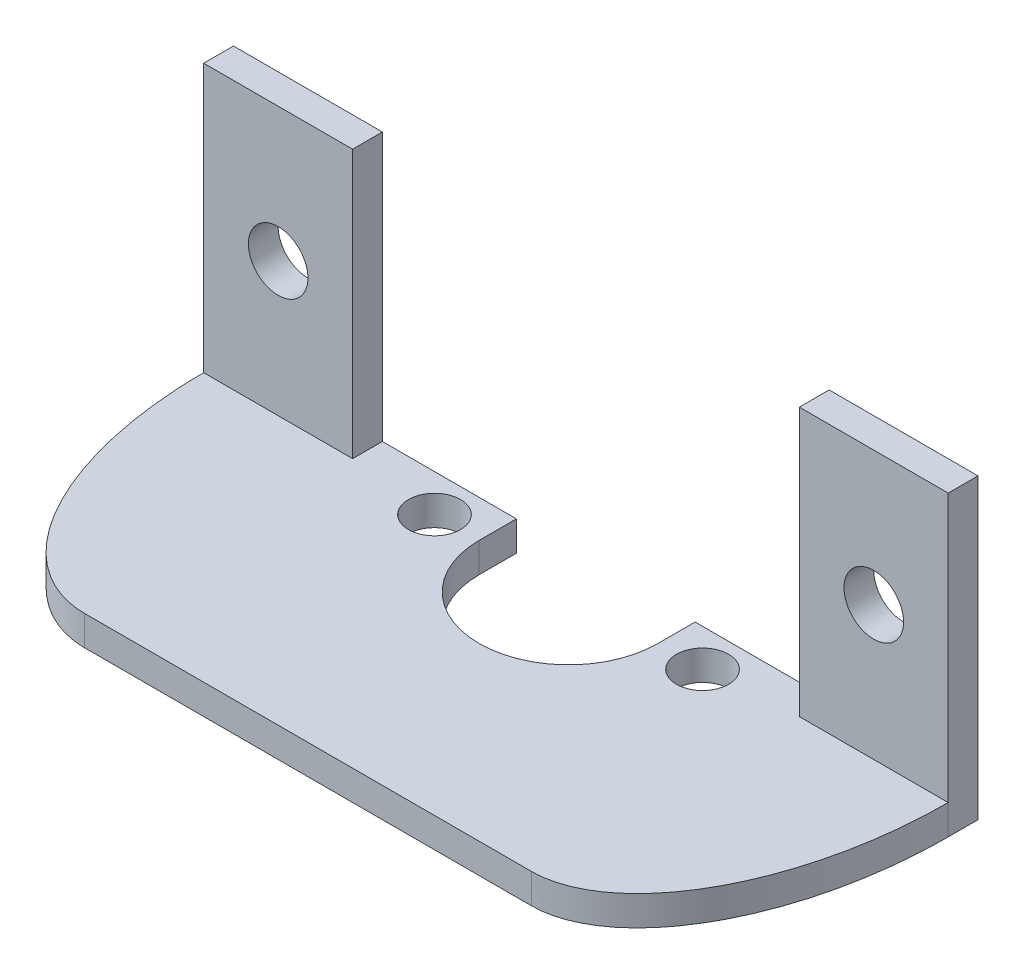
SolidWorks part; units mm, degrees
ref_plane "Front Plane" through (0, 0, 0) normal (0, 0, 1) x (1, 0, 0)
ref_plane "Top Plane" through (0, 0, 0) normal (0, 1, 0) x (1, 0, 0)
ref_plane "Right Plane" through (0, 0, 0) normal (1, 0, 0) x (0, 0, -1)
sketch "Sketch1" plane through (0, 0, 0) normal (0, 1, 0) x (1, 0, 0)
  line L1 (-25, 10) -> (25, 10)
  line L2 (-25, 10) -> (-25, -10)
  line L3 (-25, -10) -> (25, -10)
  line L4 (25, 10) -> (25, -10)
  line L5 (-25, 10) -> (25, -10) construction
  line L6 (-25, -10) -> (25, 10) construction
  point P0 (0, 0)
  dimension "D1" = 50
  dimension "D2" = 20
extrude "Boss-Extrude1" add sketch "Sketch1" along normal blind 2
sketch "Sketch2" plane through (0, 2, 0) normal (0, 1, 0) x (1, 0, 0)
  line L1 (-25, 10) -> (-15, 10)
  line L2 (-25, 10) -> (-25, 8)
  line L3 (-25, 8) -> (-15, 8)
  line L4 (-15, 10) -> (-15, 8)
  line L5 (25, 10) -> (15, 10)
  line L6 (25, 10) -> (25, 8)
  line L7 (25, 8) -> (15, 8)
  line L8 (15, 10) -> (15, 8)
  dimension "D1" = 10
  dimension "D2" = 2
  dimension "D3" = 10
  dimension "D4" = 2
extrude "Boss-Extrude2" add sketch "Sketch2" along normal blind 18
fillet "Fillet1" radius 18 1 edges at (-25, 1, 10) second distance 10 first distance on face at (-25, 7.3333, -2.6667)
fillet "Fillet2" radius 10 1 edges at (25, 1, 10) second distance 18 first distance on face at (-5, 1.25, 10)
ref_plane "Plane1" through (0, 0, -7.5) normal (0, 0, 1) x (1, 0, 0)
ref_axis "Axis2" through (-24.7222, 2, -7.5) along (1, 0, 0)
sketch "Sketch4" plane through (0, 2, 0) normal (0, 1, 0) x (1, 0, 0)
  line L0 (-24.7222, 7.5) -> (24.7222, 7.5) construction
  line L1 (0, -11.0495) -> (0, 11.0495) construction
  line L2 (-6, 7.5) -> (-6, 10)
  line L3 (15, 10) -> (-15, 10) construction
  line L4 (-6, 10) -> (6, 10)
  line L5 (6, 10) -> (6, 7.5)
  arc A1 (-6, 7.5) -> (6, 7.5) centre (0, 7.5) ccw
extrude "Cut-Extrude1" cut sketch "Sketch4" against normal through all
sketch "Sketch5" plane through (0, 2, 0) normal (0, 1, 0) x (1, 0, 0)
  line L0 (-24.7222, 7.5) -> (24.7222, 7.5) construction
  circle A0 centre (-9, 7.5) radius 1.75
  circle A1 centre (9, 7.5) radius 1.75
  dimension "D1" = 3
  dimension "D2" = 3.5
  dimension "D3" = 3.5
  dimension "D4" = 3
extrude "Cut-Extrude2" cut sketch "Sketch5" against normal through all
sketch "Sketch6" plane through (0, 0, -8) normal (0, 0, 1) x (1, 0, 0)
  line L0 (25, 20) -> (25, 2) construction
  line L1 (15, 20) -> (25, 20) construction
  line L2 (0, -11.0495) -> (0, 11.0495) construction
  circle A0 centre (20, 11) radius 2
  circle A2 centre (-20, 11) radius 2
  dimension "D1" = 4
  dimension "D2" = 5
  dimension "D3" = 9
extrude "Cut-Extrude3" cut sketch "Sketch6" against normal through all
